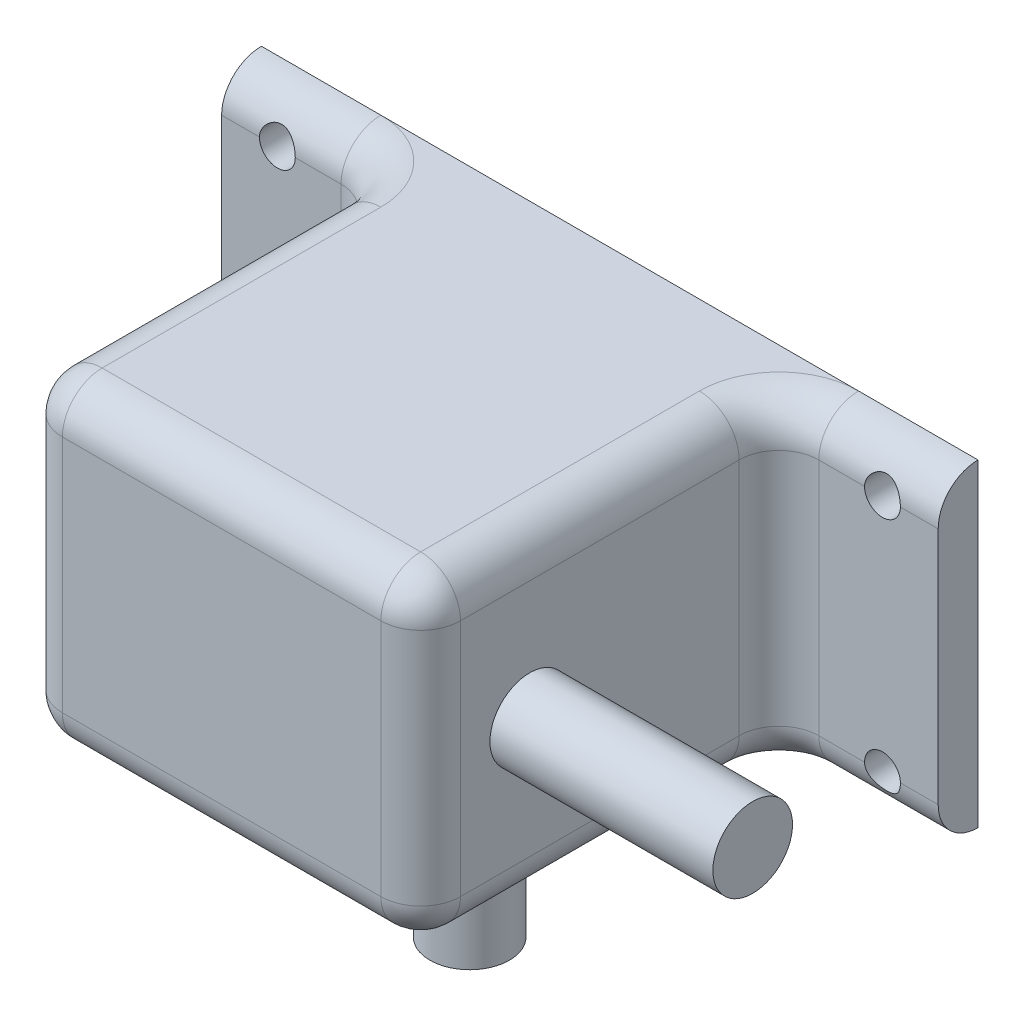
SolidWorks part; units mm, degrees
ref_plane "Front Plane" through (0, 0, 0) normal (0, 0, 1) x (1, 0, 0)
ref_plane "Top Plane" through (0, 0, 0) normal (0, 1, 0) x (1, 0, 0)
ref_plane "Right Plane" through (0, 0, 0) normal (1, 0, 0) x (0, 0, -1)
ref_plane "Plane1" through (0, -40, 0) normal (0, -1, 0) x (1, 0, 0)
sketch "Sketch1" plane through (0, -40, 0) normal (0, -1, 0) x (1, 0, 0)
  line L0 (45, 38.915) -> (-45, 38.915)
  line L1 (-45, 38.915) -> (-45, -11.085)
  line L2 (-45, -11.085) -> (45, -11.085)
  line L3 (45, -11.085) -> (45, 38.915)
extrude "Boss-Extrude1" add sketch "Sketch1" against normal blind 40
sketch "Sketch2" plane through (0, 0, 0) normal (0, 1, 0) x (-1, 0, 0)
  line L0 (45, 38.915) -> (25, 38.915)
  line L1 (25, 38.915) -> (25, -6.085)
  line L2 (25, -6.085) -> (45, -6.085)
  line L3 (45, -6.085) -> (45, 38.915)
extrude "Cut-Extrude1" cut sketch "Sketch2" against normal through all
sketch "Sketch3" plane through (0, 0, 0) normal (0, 1, 0) x (-1, 0, 0)
  line L0 (-45, 38.915) -> (-45, -6.085)
  line L1 (-45, -6.085) -> (-25, -6.085)
  line L2 (-25, -6.085) -> (-25, 38.915)
  line L3 (-25, 38.915) -> (-45, 38.915)
extrude "Cut-Extrude2" cut sketch "Sketch3" against normal through all
ref_plane "Plane2" through (0, 0, 8.915) normal (0, 0, -1) x (-1, 0, 0)
ref_plane "Plane3" through (0, 0, 23.915) normal (0, 0, -1) x (-1, 0, 0)
hole_wizard "Ø4.5 (4.5) Diameter Hole1" positions "Sketch7" profile "Sketch6" hole size "Ø4.5" standard "ANSI Metric"
sketch "Sketch7" plane through (0, 0, -6.085) normal (0, 0, 1) x (1, 0, 0)
  point P0 (38, -5)
  point P1 (-38, -35)
  point P2 (-38, -5)
  point P3 (38, -35)
sketch "Sketch6" plane through (38, -5, -6.085) normal (1, 0, 0) x (0, -1, 0)
  line L0 (0, 0) -> (0, 5)
  line L1 (0, 5) -> (2.25, 5)
  line L2 (2.25, 5) -> (2.25, 0)
  line L5 (2.25, 0) -> (0, 0)
  line L11 (0, -6.35) -> (0, 107.95) construction
  dimension "Thru Hole Dia." = 4.5
  dimension "Thru Hole Depth" = 5
fillet "Fillet1" radius 5 14 edges at (-35, -40, -6.085) (-35, 0, -6.085) (35, 0, -6.085) (35, -40, -6.085) (-25, -20, -6.085) (25, 0, 16.415) (25, -20, -6.085) (-25, 0, 16.415) (-25, -40, 16.415) (-25, -20, 38.915) (0, 0, 38.915) (25, -40, 16.415) (0, -40, 38.915) (25, -20, 38.915)
scale "Scale1" scale about centroid uniform scaling yes scale factor 2.8
sketch "Sketch12" plane through (0, -76, 0) normal (0, -1, 0) x (1, 0, 0)
  circle A0 centre (0, 0) radius 14
  dimension "D1" = 28
extrude "Boss-Extrude2" add sketch "Sketch12" along normal blind 70
sketch "Sketch13" plane through (70, 0, 0) normal (1, 0, 0) x (0, 0, -1)
  circle A0 centre (-48.8768, -20) radius 14
  dimension "D1" = 28
extrude "Boss-Extrude3" add sketch "Sketch13" along normal blind 78.4
